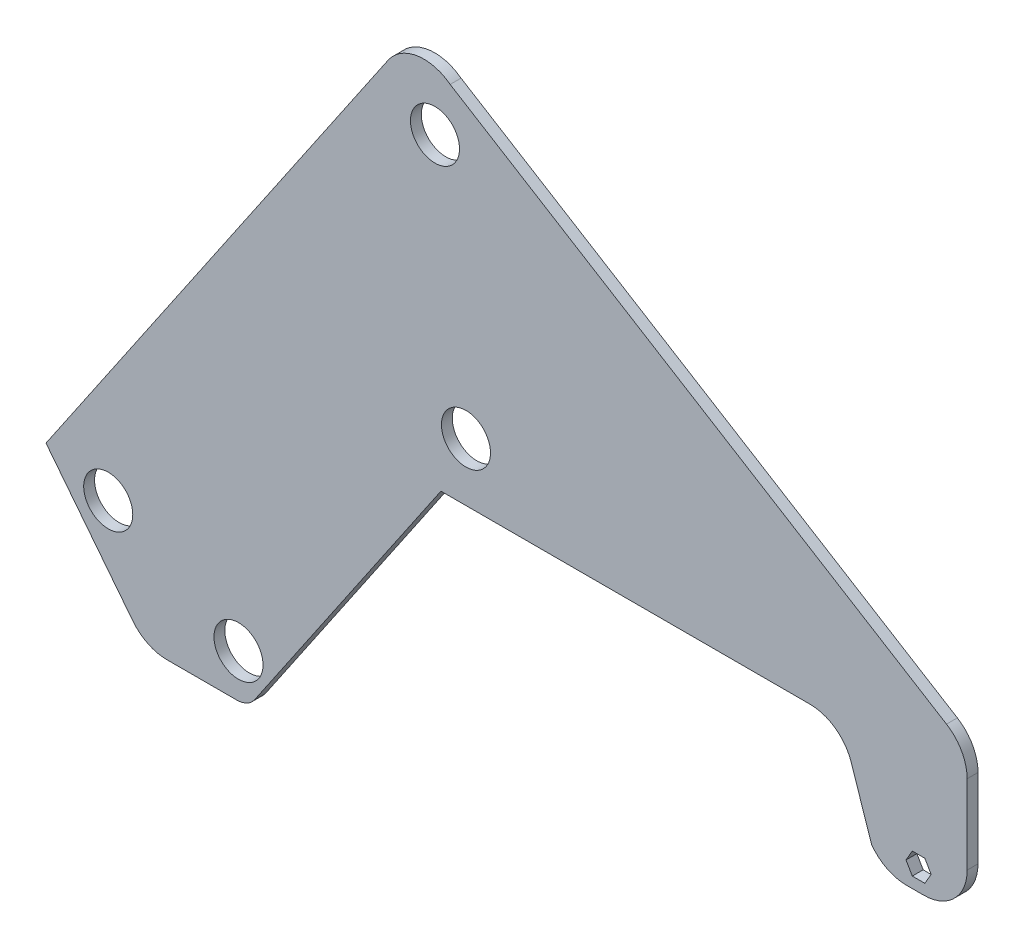
SolidWorks part; units mm, degrees
other "Markup1"
sketch "Sketch1" plane through (-441.7893, 331.8239, 6.35) normal (-0.0431, 0.0102, 0.999) x (0.9985, 0.0354, 0.0427)
sketch "Sketch2" plane through (-413.6701, 343.933, 6.35) normal (-0.0431, 0.0102, 0.999) x (0.9985, 0.0354, 0.0427)
sketch "Sketch3" plane through (-436.3774, 318.5567, 6.35) normal (-0.0431, 0.0102, 0.999) x (0.9985, 0.0354, 0.0427)
sketch "Sketch5" plane through (-436.3774, 318.5567, 6.35) normal (-0.0431, 0.0102, 0.999) x (0.9985, 0.0354, 0.0427)
other "Markup2"
sketch "Sketch4" plane through (102.4721, 318.5567, 6.35) normal (0.9364, 0.1073, 0.3342) x (0.3416, -0.0598, -0.9379)
sketch "Sketch6" plane through (102.4721, 318.5567, 6.35) normal (0.9364, 0.1073, 0.3342) x (0.3416, -0.0598, -0.9379)
ref_plane "Front Plane" through (0, 0, 0) normal (0, 0, 1) x (1, 0, 0)
ref_plane "Top Plane" through (0, 0, 0) normal (0, 1, 0) x (1, 0, 0)
ref_plane "Right Plane" through (0, 0, 0) normal (1, 0, 0) x (0, 0, -1)
sketch "Model" plane through (0, 0, 0) normal (0, 0, 1) x (1, 0, 0)
  line L1 (-205.3388, 104.6502) -> (-2.1388, 104.6502)
  line L3 (-314.2383, -55.3595) -> (-205.3388, 104.6502)
  line L4 (-236.3032, 307.4477) -> (-436.3774, 13.472)
  line L5 (-436.3774, 13.472) -> (-385.5815, -51.2028)
  line L13 (81.3935, 53.8502) -> (77.7274, 60.2002)
  line L14 (77.7274, 60.2002) -> (70.395, 60.2002)
  line L15 (70.395, 60.2002) -> (66.7288, 53.8502)
  line L16 (66.7288, 53.8502) -> (70.395, 47.5002)
  line L17 (70.395, 47.5002) -> (77.7274, 47.5002)
  line L18 (77.7274, 47.5002) -> (81.3935, 53.8502)
  line L19 (-365.606, -60.914) -> (-324.7375, -60.914)
  line L20 (-871.0211, -88.854) -> (370.1019, -88.854) construction
  line L22 (102.4721, 66.5502) -> (102.4721, 83.8724)
  line L27 (67.0531, 41.1502) -> (77.0721, 41.1502)
  line L28 (-399.9752, 2.586) -> (-323.7752, -35.514) construction
  line L29 (-323.7752, -35.514) -> (-190.7071, 138.5169) construction
  line L30 (-190.7071, 138.5169) -> (-208.8329, 283.4378) construction
  line L31 (-208.8329, 283.4378) -> (-399.9752, 2.586) construction
  line L32 (46.5921, 51.5001) -> (34.6564, 87.2866)
  line L33 (10.5612, 104.6502) -> (-11.3966, 104.6502)
  line L34 (102.4721, 83.8724) -> (102.4721, 112.8538)
  line L35 (90.397, 134.478) -> (-199.9496, 313.3896)
  circle A9 centre (-323.7752, -35.514) radius 14.351
  circle A10 centre (-399.9752, 2.586) radius 14.351
  circle A12 centre (-190.7071, 138.5169) radius 14.351
  circle A22 centre (-208.8329, 283.4378) radius 14.351
  circle A24 centre (74.0612, 53.8502) radius 6.35 construction
  arc A31 (-324.7375, -60.914) -> (-314.2383, -55.3595) centre (-324.7375, -48.214) ccw
  arc A40 (46.5921, 51.5001) -> (67.0531, 41.1502) centre (67.0531, 66.5502) ccw
  arc A43 (77.0721, 41.1502) -> (102.4721, 66.5502) centre (77.0721, 66.5502) ccw
  arc A44 (-236.3032, 307.4477) -> (-199.9496, 313.3896) centre (-215.305, 293.1567) cw
  arc A45 (-365.606, -60.914) -> (-385.5815, -51.2028) centre (-365.606, -35.514) cw
  arc A46 (34.6564, 87.2866) -> (10.5612, 104.6502) centre (10.5612, 79.2502) ccw
  arc A47 (102.4721, 112.8538) -> (90.397, 134.478) centre (77.0721, 112.8538) ccw
  point P31 (-221.2548, 329.5588)
  point P34 (100.2935, -12.8222)
  point P43 (-377.9543, -60.914)
  point P59 (174.831, 53.8502)
  dimension "D3" = 38.1
  dimension "D4" = 104.6502
  dimension "D5" = 76.2
  dimension "D6" = 25.4
  dimension "D7" = 12.7
  dimension "D8" = 28.702
  dimension "D11" = 139.7
  dimension "D12" = 27.94
  dimension "D21" = 124.238
  dimension "D13" = 12.7
  dimension "D16" = 355.6
  dimension "D23" = 25.4
  dimension "D24" = 25.4
  dimension "D26" = 25.4
  dimension "D14" = 406.4
  dimension "D20" = 215.9
  dimension "D29" = 25.4
  dimension "D31" = 25.4
  dimension "D25" = 88.9
  dimension "D9" = 19.05
  dimension "D10" = 146.05
  dimension "D15" = 33.8667
  dimension "D17" = 339.725
  dimension "D18" = 219.075
  dimension "D19" = 50.8
  dimension "D22" = 25.4
  dimension "D27" = 53.2168
  dimension "D28" = 12.7
  dimension "D30" = 55.88
extrude "Boss-Extrude1" add sketch "Model" along normal blind 6.35 contours L5 L3 L1 L4 A22 A9 A10 A12 region at (-265.237, 28.3535, 0)
